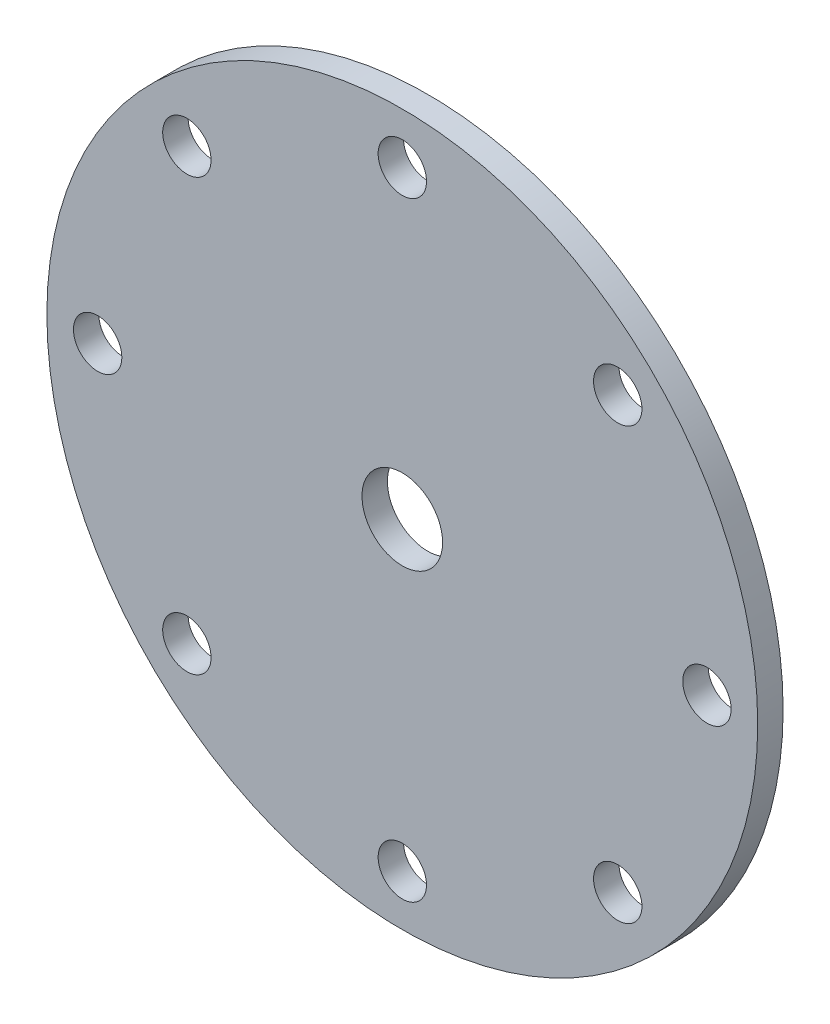
SolidWorks part; units mm, degrees
ref_plane "Front Plane" through (0, 0, 0) normal (0, 0, 1) x (1, 0, 0)
ref_plane "Top Plane" through (0, 0, 0) normal (0, 1, 0) x (1, 0, 0)
ref_plane "Right Plane" through (0, 0, 0) normal (1, 0, 0) x (0, 0, -1)
sketch "Sketch1" plane through (0, 0, 0) normal (0, 0, 1) x (1, 0, 0)
  line L0 (0, 70) -> (0, -70) construction
  line L1 (-70, 0) -> (70, 0) construction
  line L2 (-42.4264, 42.4264) -> (42.4264, -42.4264) construction
  line L3 (-42.4264, -42.4264) -> (42.4264, 42.4264) construction
  circle A0 centre (0, 0) radius 70
  circle A1 centre (0, 0) radius 7.9375
  circle A2 centre (0, 60) radius 4.7625
  circle A6 centre (42.4264, 42.4264) radius 4.7625
  circle A7 centre (60, 0) radius 4.7625
  circle A8 centre (42.4264, -42.4264) radius 4.7625
  circle A9 centre (0, -60) radius 4.7625
  circle A10 centre (-42.4264, -42.4264) radius 4.7625
  circle A11 centre (-60, 0) radius 4.7625
  circle A12 centre (-42.4264, 42.4264) radius 4.7625
  dimension "D1" = 140
  dimension "D2" = 15.875
  dimension "D3" = 9.525
  dimension "D6" = 10
  dimension "D4" = 10
  dimension "D5" = 8
extrude "Rotor Disc" add sketch "Sketch1" along normal blind 5 contours A0 A12 A11 A10 A8 A7 A6 A1 A2 region at (-68.0201, 0, 0)
